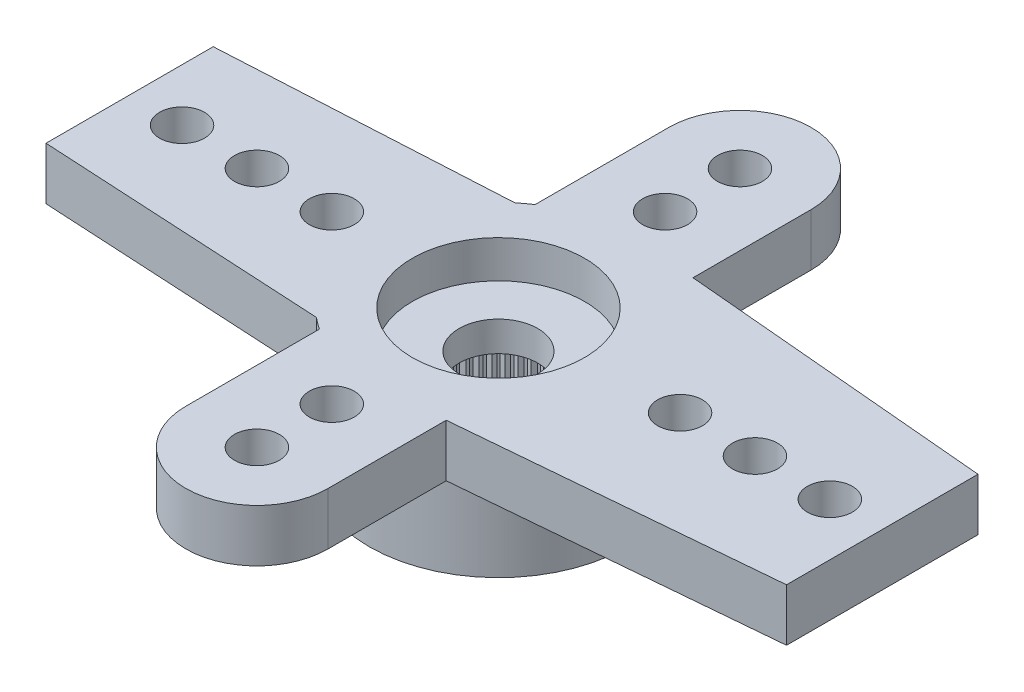
SolidWorks part; units mm, degrees
material "PVC Rígido"
ref_plane "Plano frontal" through (0, 0, 0) normal (0, 0, 1) x (1, 0, 0)
ref_plane "Plano superior" through (0, 0, 0) normal (0, 1, 0) x (1, 0, 0)
ref_plane "Plano direito" through (0, 0, 0) normal (1, 0, 0) x (0, 0, -1)
sketch "Esboço1" plane through (0, 0, 0) normal (0, 1, 0) x (1, 0, 0)
  line L0 (0, 0) -> (-14.05, 0) construction
  line L1 (-14.1591, 1.997) -> (-2.2091, 2.65)
  line L2 (-2.2091, -2.65) -> (-14.1591, -1.997)
  arc A0 (-2.2091, -2.65) -> (-2.2091, 2.65) centre (0, 0) ccw
  arc A1 (-14.1591, 1.997) -> (-14.1591, -1.997) centre (-14.05, 0) ccw
  dimension "D1" = 6.9
  dimension "D2" = 4
  dimension "D3" = 19.5
  dimension "D4" = 5.3
extrude "Ressalto-extrusão1" add sketch "Esboço1" against normal blind 1.4
sketch "Esboço2" plane through (0, -1.4, 0) normal (0, -1, 0) x (1, 0, 0)
  arc A0 (-2.2091, -2.65) -> (-2.2091, 2.65) centre (0, 0) ccw construction
  circle A1 centre (0, 0) radius 3.45
extrude "Ressalto-extrusão2" add sketch "Esboço2" along normal offset from surface (2.4 mm away) 3.8 up to face at (-7.242, 0, 0)
hole_wizard "Furo1" positions "Esboço9" profile "Esboço10" legacy end condition through all
sketch "Esboço9" plane through (0, 0, 0) normal (0, 1, 0) x (1, 0, 0)
  line L1 (-14.45, 0) -> (0, 0) construction
  arc A2 (-14.1591, 1.997) -> (-14.1591, -1.997) centre (-14.05, 0) ccw construction
  point P0 (-14.45, 0)
  point P19 (-16.05, 0)
  dimension "D1" = 1.6
sketch "Esboço10" plane through (-14.45, 0, 0) normal (1, 0, 0) x (0, 0, 1)
  line L0 (0, 0) -> (0, 3.8)
  line L1 (0, 3.8) -> (0.6, 3.8)
  line L2 (0.6, 3.8) -> (0.6, 0)
  line L3 (0.6, 0) -> (0, 0)
  line L4 (0, 110) -> (0, -10) construction
  dimension "Diameter" = 1.2
  dimension "Depth" = 3.8
pattern_linear "Padrão linear1" count 6 spacing 2 along (1, 0, 0) of "Furo1"
sketch "Esboço12" plane through (0, 0, 0) normal (0, 1, 0) x (1, 0, 0)
  line L0 (0.3041, 3.4366) -> (16.6263, 1.9922)
  line L1 (16.6263, -1.9922) -> (0.3041, -3.4366)
  arc A0 (-2.2091, -2.65) -> (-2.2091, 2.65) centre (0, 0) ccw construction
  arc A1 (0.3041, -3.4366) -> (0.3041, 3.4366) centre (0, 0) ccw
  arc A2 (16.6263, 1.9922) -> (16.6263, -1.9922) centre (16.45, 0) cw
  arc A3 (-14.1591, 1.997) -> (-14.1591, -1.997) centre (-14.05, 0) ccw construction
  dimension "D1" = 2
  dimension "D2" = 34.5
extrude "Ressalto-extrusão3" add sketch "Esboço12" against normal up to surface (1.4 mm away) up to face at (-12.45, -1.4, 0.6)
hole_wizard "Furo2" positions "Esboço13" profile "Esboço14" legacy end condition through all
sketch "Esboço13" plane through (0, 0, 0) normal (0, 1, 0) x (1, 0, 0)
  line L0 (0, 0) -> (16.85, 0) construction
  arc A0 (16.6263, -1.9922) -> (16.6263, 1.9922) centre (16.45, 0) ccw construction
  point P0 (16.85, 0)
  point P6 (18.45, 0)
  dimension "D1" = 1.6
sketch "Esboço14" plane through (16.85, 0, 0) normal (1, 0, 0) x (0, 0, 1)
  line L0 (0, 0) -> (0, 3.8)
  line L1 (0, 3.8) -> (0.6, 3.8)
  line L2 (0.6, 3.8) -> (0.6, 0)
  line L3 (0.6, 0) -> (0, 0)
  line L4 (0, 110) -> (0, -10) construction
  dimension "Diameter" = 1.2
  dimension "Depth" = 3.8
pattern_linear "Padrão linear2" count 7 spacing 2 along (-1, 0, 0) of "Furo2"
sketch "Esboço16" plane through (0, 0, 0) normal (0, 1, 0) x (1, 0, 0)
  line L0 (0, -6.45) -> (0, 6.45) construction
  line L1 (-1.9, -6.45) -> (-1.9, 6.45)
  line L2 (1.9, -6.45) -> (1.9, 6.45)
  arc A0 (-1.9, -6.45) -> (1.9, -6.45) centre (0, -6.45) ccw
  arc A1 (1.9, 6.45) -> (-1.9, 6.45) centre (0, 6.45) ccw
  point P2 (0, 0)
  dimension "D2" = 16.7
  dimension "D1" = 3.8
extrude "Ressalto-extrusão4" add sketch "Esboço16" against normal up to surface (1.4 mm away) up to face at (14.85, -1.4, 0.6)
hole_wizard "Furo3" positions "Esboço17" profile "Esboço18" legacy end condition through all
sketch "Esboço17" plane through (0, 0, 0) normal (0, 1, 0) x (1, 0, 0)
  point P0 (0, -6.45)
sketch "Esboço18" plane through (0, 0, 6.45) normal (1, 0, 0) x (0, 0, 1)
  line L0 (0, 0) -> (0, 3.8)
  line L1 (0, 3.8) -> (0.6, 3.8)
  line L2 (0.6, 3.8) -> (0.6, 0)
  line L3 (0.6, 0) -> (0, 0)
  line L4 (0, 110) -> (0, -10) construction
  dimension "Diameter" = 1.2
  dimension "Depth" = 3.8
pattern_linear "Padrão linear3" count 2 spacing 2 along (0, 0, -1) of "Furo3"
pattern_circular "PadrãoCircular1" count 2 over 360 about axis through (0, -1.4, 0) along (0, 1, 0) of "Padrão linear3"
hole_wizard "Furo4" positions "Esboço3" profile "Esboço4" legacy
sketch "Esboço3" plane through (0, -3.8, 0) normal (0, -1, 0) x (-1, 0, 0)
  point P0 (0, 0)
sketch "Esboço4" plane through (0, -3.8, 0) normal (1, 0, 0) x (0, 0, -1)
  line L0 (0, 0) -> (0, 2)
  line L1 (0, 2) -> (2.475, 2)
  line L2 (2.475, 2) -> (2.475, 0)
  line L3 (2.475, 0) -> (0, 0)
  line L4 (0, 110) -> (0, -10) construction
  dimension "Diameter" = 4.95
  dimension "Depth" = 2
hole_wizard "Furo5" positions "Esboço5" profile "Esboço6" legacy
sketch "Esboço5" plane through (0, 0, 0) normal (0, 1, 0) x (1, 0, 0)
  point P0 (0, 0)
sketch "Esboço6" plane through (0, 0, 0) normal (1, 0, 0) x (0, 0, 1)
  line L0 (0, 0) -> (0, 1)
  line L1 (0, 1) -> (2.3, 1)
  line L2 (2.3, 1) -> (2.3, 0)
  line L3 (2.3, 0) -> (0, 0)
  line L4 (0, 110) -> (0, -10) construction
  dimension "Diameter" = 4.6
  dimension "Depth" = 1
hole_wizard "Furo6" positions "Esboço7" profile "Esboço8" legacy end condition through all
sketch "Esboço7" plane through (0, 0, 0) normal (0, 1, 0) x (1, 0, 0)
  point P0 (0, 0)
sketch "Esboço8" plane through (0, 0, 0) normal (1, 0, 0) x (0, 0, 1)
  line L0 (0, 0) -> (0, 3.8)
  line L1 (0, 3.8) -> (1.05, 3.8)
  line L2 (1.05, 3.8) -> (1.05, 0)
  line L3 (1.05, 0) -> (0, 0)
  line L4 (0, 110) -> (0, -10) construction
  dimension "Diameter" = 2.1
  dimension "Depth" = 3.8
sketch "Esboço11" plane through (0, -3.8, 0) normal (0, -1, 0) x (1, 0, 0)
  line L0 (-0.0981, 2.4731) -> (0, 2.375)
  line L1 (0, 2.375) -> (0.0981, 2.4731)
  line L2 (0, 0) -> (0, 2.475) construction
  circle A0 centre (0, 0) radius 2.375 construction
  circle A1 centre (0, 0) radius 2.475
  arc A2 (0.0981, 2.4731) -> (-0.0981, 2.4731) centre (0, 0) ccw
  dimension "D3" = 4.75
  dimension "D2" = 0.1
  dimension "D1" = 0
extrude "Ressalto-extrusão5" add sketch "Esboço11" against normal up to surface (2 mm away) up to face at (0, -1.8, 1.05)
pattern_circular "PadrãoCircular2" count 60 over 360 about axis through (0, -1.4, 0) along (0, 1, 0) of "Ressalto-extrusão5"
sketch "Sketch1" plane through (0, 0, 0) normal (0, 1, 0) x (1, 0, 0)
  line L1 (-2.2091, 2.65) -> (-14.1591, 1.997) construction
  line L2 (-14.1591, -1.997) -> (-2.2091, -2.65) construction
  line L3 (-9.85, -2.2325) -> (-19.136, -2.2325)
  line L4 (-19.136, -2.2325) -> (-19.136, 2.3801)
  line L5 (-19.136, 2.3801) -> (-9.85, 2.2325)
  line L12 (-9.85, 2.2325) -> (-9.85, -2.2325)
  line L13 (0, 3.5355) -> (0, -5.5205) construction
  line L18 (10.25, 2.5565) -> (10.25, -2.5565)
  line L19 (16.6263, 1.9922) -> (1.9, 3.2953) construction
  line L20 (1.9, -3.2953) -> (16.6263, -1.9922) construction
  line L21 (10.25, -2.5565) -> (20.1208, -2.5565)
  line L22 (20.1208, -2.5565) -> (20.1208, 2.5565)
  line L23 (20.1208, 2.5565) -> (10.25, 2.5565)
  circle A3 centre (-10.45, 0) radius 0.6 construction
  point P18 (-9.85, 0)
extrude "Cut-Extrude3" cut sketch "Sketch1" against normal blind 10
